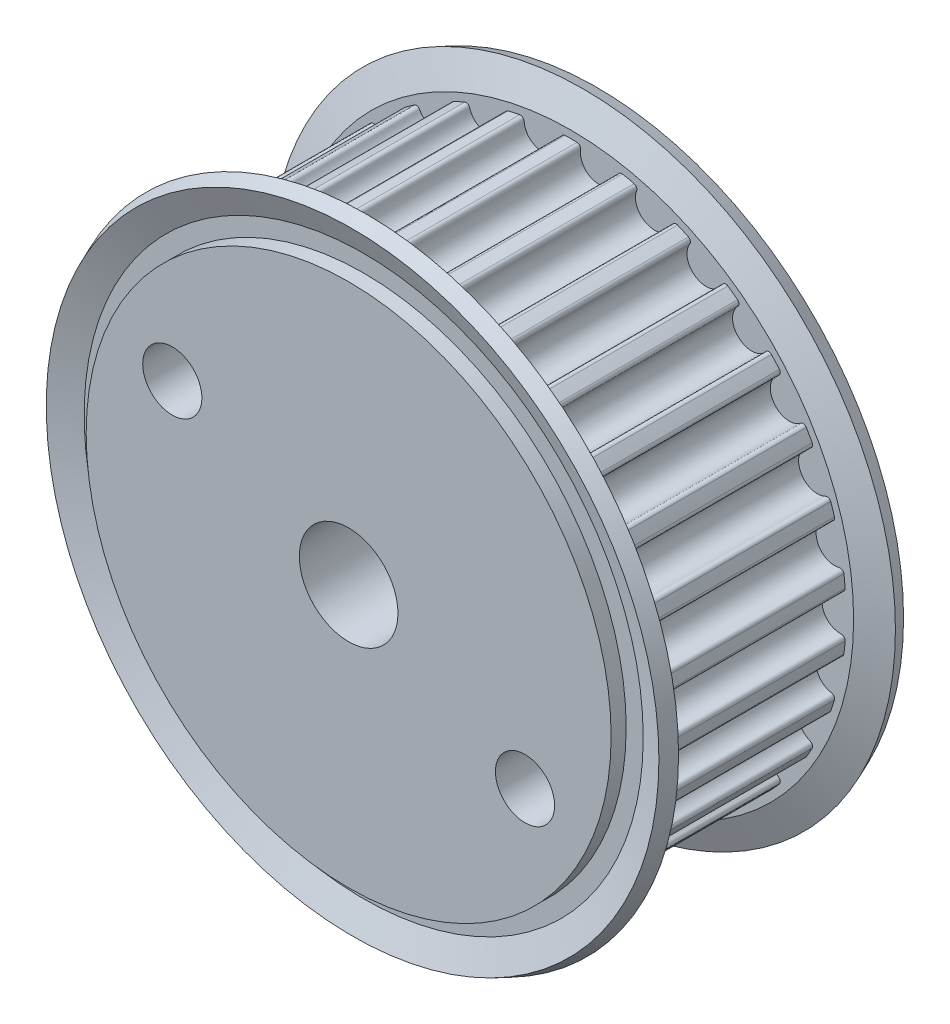
SolidWorks part; units mm, degrees
ref_plane "前视基准面" through (0, 0, 0) normal (0, 0, 1) x (1, 0, 0)
ref_plane "上视基准面" through (0, 0, 0) normal (0, 1, 0) x (1, 0, 0)
ref_plane "右视基准面" through (0, 0, 0) normal (1, 0, 0) x (0, 0, -1)
ref_axis "基准轴1" through (0, 0, 55) along (0, 0, -1)
sketch "SketchRevolveGearBelt01" plane through (0, 0, 0) normal (1, 0, 0) x (0, 0, -1)
  line L0 (0, 0) -> (1, 0) construction
  line L1 (6.4008, 0) -> (6.4008, 13.3069)
  line L2 (6.4008, 13.3069) -> (5.6388, 13.3069)
  line L3 (5.6388, 13.3069) -> (5.6388, 14.1713)
  line L4 (5.6388, 14.1713) -> (6.2015, 15.5299)
  line L5 (6.2015, 15.5299) -> (5.4975, 15.8215)
  line L6 (5.4975, 15.8215) -> (4.8768, 14.3229)
  line L7 (4.8768, 14.3229) -> (4.8768, 13.9419)
  line L8 (4.8768, 13.9419) -> (-4.8768, 13.9419)
  line L9 (-4.8768, 13.9419) -> (-4.8768, 14.3229)
  line L10 (-4.8768, 14.3229) -> (-5.4975, 15.8215)
  line L11 (-5.4975, 15.8215) -> (-6.2015, 15.5299)
  line L12 (-6.2015, 15.5299) -> (-5.6388, 14.1713)
  line L13 (-5.6388, 14.1713) -> (-5.6388, 13.3069)
  line L14 (-5.6388, 13.3069) -> (-6.4008, 13.3069)
  line L15 (-6.4008, 13.3069) -> (-6.4008, 0)
  line L16 (-6.4008, 0) -> (6.4008, 0)
  dimension "GearBeltFlange1OutsideLength" = 0.8644
  dimension "GearBeltFlange1X" = 0.5627
  dimension "GearBeltFlange1Y" = 1.3586
  dimension "GearBeltFlangeThickness" = 0.762
  dimension "GearBeltFlangeInside" = 0.381
  dimension "GearBeltOutsideDiameter" = 13.9419
  dimension "GearBeltFlange2X" = 0.5627
revolve "GearBelt01" add sketch "SketchRevolveGearBelt01" angle 360 about L0
sketch "SketchToothGearBelt01" plane through (0, 0, 0) normal (0, 0, 1) x (1, 0, 0)
  arc A0 (13.8935, 1.162) -> (13.8935, -1.162) centre (0, 0) cw
  spline S0 degree 3 poles (13.8935, -1.162) (13.8944, -1.1516) (13.8944, -1.1357) (13.8918, -1.1148) (13.8886, -1.0994) (13.8841, -1.0843) (13.8784, -1.0695) (13.8714, -1.0553) (13.8634, -1.0418) (13.8542, -1.0289) (13.844, -1.0168) (13.8329, -1.0057) (13.8209, -0.9954) (13.808, -0.9862) (13.7945, -0.9781) (13.7803, -0.9712) (13.7656, -0.9654) (13.7505, -0.9609) (13.735, -0.9576) (13.7194, -0.9556) (13.6903, -0.9547) (13.6423, -0.9556) (13.5752, -0.953) (13.503, -0.9442) (13.4317, -0.9299) (13.3617, -0.91) (13.2935, -0.8847) (13.2275, -0.8541) (13.1641, -0.8184) (13.1036, -0.7779) (13.0466, -0.7328) (12.9932, -0.6834) (12.9439, -0.6299) (12.8989, -0.5727) (12.8585, -0.5122) (12.8231, -0.4487) (12.7926, -0.3826) (12.7675, -0.3143) (12.7478, -0.2443) (12.7336, -0.1729) (12.725, -0.1007) (12.7231, -0.0476) (12.7232, -0.014) (12.7232, 0) (12.7232, 0.014) (12.7231, 0.0476) (12.725, 0.1007) (12.7336, 0.1729) (12.7478, 0.2443) (12.7675, 0.3143) (12.7926, 0.3826) (12.8231, 0.4487) (12.8585, 0.5122) (12.8989, 0.5727) (12.9439, 0.6299) (12.9932, 0.6834) (13.0466, 0.7328) (13.1036, 0.7779) (13.1641, 0.8184) (13.2275, 0.8541) (13.2935, 0.8847) (13.3617, 0.91) (13.4317, 0.9299) (13.503, 0.9442) (13.5752, 0.953) (13.6423, 0.9556) (13.6903, 0.9547) (13.7194, 0.9556) (13.735, 0.9576) (13.7505, 0.9609) (13.7656, 0.9654) (13.7803, 0.9712) (13.7945, 0.9781) (13.808, 0.9862) (13.8209, 0.9954) (13.8329, 1.0057) (13.844, 1.0168) (13.8542, 1.0289) (13.8634, 1.0418) (13.8714, 1.0553) (13.8784, 1.0695) (13.8841, 1.0843) (13.8886, 1.0994) (13.8918, 1.1148) (13.8944, 1.1357) (13.8944, 1.1516) (13.8935, 1.162) knots 0 0 0 0 0.008513 0.012769 0.017025 0.021281 0.025538 0.029794 0.03405 0.038306 0.042563 0.046819 0.051075 0.055331 0.059588 0.063844 0.0681 0.072356 0.076613 0.080869 0.085125 0.100157 0.119771 0.139386 0.159 0.178614 0.198229 0.217843 0.237457 0.257071 0.276686 0.2963 0.315914 0.335529 0.355143 0.374757 0.394372 0.413986 0.4336 0.453214 0.472829 0.492443 0.496222 0.5 0.503778 0.507557 0.527171 0.546786 0.5664 0.586014 0.605628 0.625243 0.644857 0.664471 0.684086 0.7037 0.723314 0.742929 0.762543 0.782157 0.801771 0.821386 0.841 0.860614 0.880229 0.899843 0.914875 0.919131 0.923387 0.927644 0.9319 0.936156 0.940412 0.944669 0.948925 0.953181 0.957437 0.961694 0.96595 0.970206 0.974462 0.978719 0.982975 0.987231 0.991487 1 1 1 1
extrude "ToothExtrudeCutGearBelt01" cut sketch "SketchToothGearBelt01" against normal blind 4.8768 and the other way blind 4.8768
pattern_circular "PatternGearBelt01" count 30 every 12 about axis through (0, 0, 55) along (0, 0, -1) of "ToothExtrudeCutGearBelt01"
sketch "BoreRevolveSketch" plane through (0, 0, 0) normal (1, 0, 0) x (0, 0, -1)
  line L0 (0, 0) -> (1, 0) construction
  line L1 (-6.4008, 0) -> (6.4008, 0)
  line L2 (6.4008, 0) -> (6.4008, 2.5)
  line L3 (6.4008, 2.5) -> (-6.4008, 2.5)
  line L4 (-6.4008, 2.5) -> (-6.4008, 0)
  dimension "TaperSide1" = 2.5
  dimension "TaperSide2" = 2.5
revolve "BoreRevolveCut" cut sketch "BoreRevolveSketch" angle 360 about L0
sketch "AuxiliarySketchGearBelt01" plane through (0, 0, 0) normal (0, 0, 1) x (1, 0, 0)
  circle A0 centre (0, 0) radius 14.3229 construction
  dimension "PitchDiameter" = 28.6458
sketch "草图1" plane through (0, 0, -6.4008) normal (0, 0, -1) x (-1, 0, 0)
  circle A0 centre (-8.941, -4.4787) radius 1.5
  circle A1 centre (8.941, 4.4787) radius 1.5
extrude "切除-拉伸1" cut sketch "草图1" against normal blind 17
